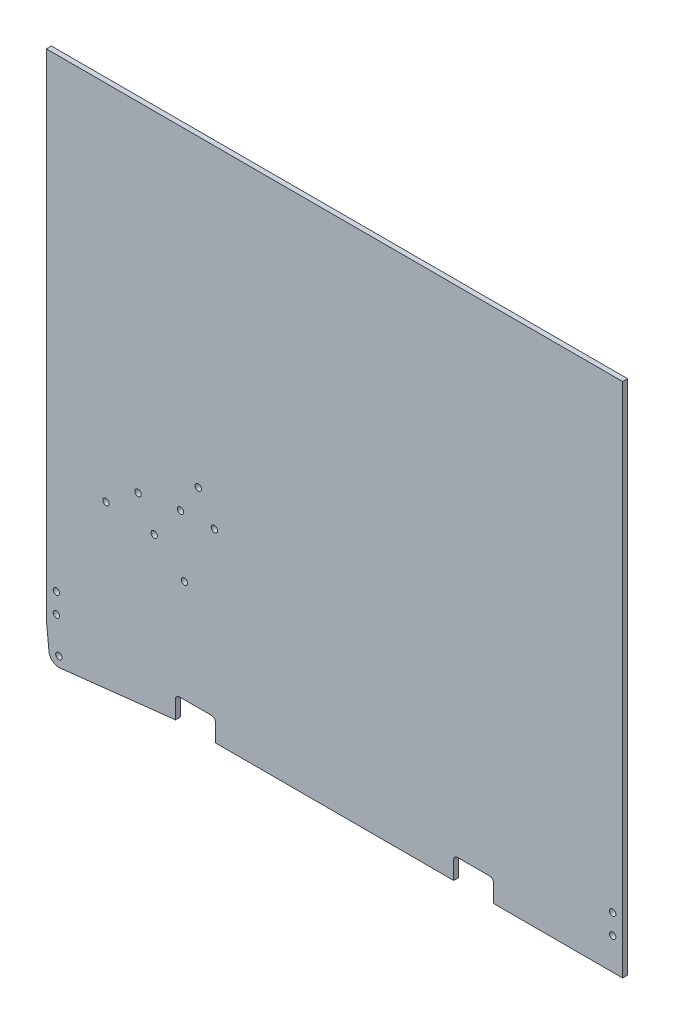
SolidWorks part; units mm, degrees
ref_plane "Front Plane" through (0, 0, 0) normal (0, 0, 1) x (1, 0, 0)
ref_plane "Top Plane" through (0, 0, 0) normal (0, 1, 0) x (1, 0, 0)
ref_plane "Right Plane" through (0, 0, 0) normal (1, 0, 0) x (0, 0, -1)
sketch "Sketch1" plane through (0, 0, 0) normal (0, 0, 1) x (1, 0, 0)
  line L0 (82.55, -20.32) -> (82.55, -6.35)
  line L2 (0, 0) -> (0, 309.88)
  line L3 (0, 309.88) -> (368.3, 309.88)
  line L4 (368.3, -20.32) -> (368.3, 309.88)
  line L5 (82.55, -6.35) -> (107.95, -6.35)
  line L6 (107.95, -6.35) -> (107.95, -20.32)
  line L7 (107.95, -20.32) -> (260.35, -20.32)
  line L8 (260.35, -20.32) -> (260.35, -6.35)
  line L9 (260.35, -6.35) -> (285.75, -6.35)
  line L10 (285.75, -6.35) -> (285.75, -20.32)
  line L11 (285.75, -20.32) -> (368.3, -20.32)
  line L12 (361.95, 12.7) -> (368.3, 12.7) construction
  line L13 (0, 0) -> (6.35, 0) construction
  line L14 (0.0315, -6.9818) -> (1.619, -22.8568)
  line L15 (8.6391, -28.5361) -> (82.55, -20.32)
  line L16 (0, 0) -> (0, -6.35)
  line L17 (85.725, 97.155) -> (82.9754, 95.5675) construction
  line L18 (97.0634, 115.6163) -> (58.5686, 93.3913) construction
  line L19 (97.0634, 115.6163) -> (107.3822, 97.7437) construction
  line L20 (58.5686, 93.3913) -> (68.8873, 75.5187) construction
  line L21 (107.3822, 97.7437) -> (68.8873, 75.5187) construction
  line L22 (97.0634, 115.6163) -> (68.8873, 75.5187) construction
  line L23 (58.5686, 93.3913) -> (107.3822, 97.7437) construction
  line L24 (7.9375, -22.225) -> (88.2169, 59.1366) construction
  circle A0 centre (6.35, 0) radius 2.032
  circle A1 centre (6.35, 12.7) radius 2.032
  circle A2 centre (361.95, 0) radius 2.032
  circle A3 centre (361.95, 12.7) radius 2.032
  arc A5 (1.619, -22.8568) -> (8.6391, -28.5361) centre (7.9375, -22.225) ccw
  circle A6 centre (7.9375, -22.225) radius 2.032
  arc A7 (0, -6.35) -> (0.0315, -6.9818) centre (6.35, -6.35) ccw
  circle A8 centre (38.1, 78.105) radius 2.032
  circle A9 centre (85.725, 97.155) radius 2.032
  circle A10 centre (58.5686, 93.3913) radius 2.032
  circle A11 centre (68.8873, 75.5187) radius 2.032
  circle A12 centre (107.3822, 97.7437) radius 2.032
  circle A13 centre (97.0634, 115.6163) radius 2.032
  circle A14 centre (88.2169, 59.1366) radius 2.032
  dimension "D6" = 4.064
  dimension "D10" = 6.35
  dimension "D11" = 4.064
  dimension "D17" = 38.1
  dimension "D2" = 330.2
  dimension "D3" = 13.97
  dimension "D4" = 25.4
  dimension "D5" = 152.4
  dimension "D7" = 12.7
  dimension "D8" = 6.35
  dimension "D9" = 20.32
  dimension "D12" = 22.225
  dimension "D13" = 1.5875
  dimension "D14" = 82.55
  dimension "D15" = 368.3
  dimension "D16" = 6.35
  dimension "D18" = 98.425
  dimension "D19" = 47.625
  dimension "D20" = 19.05
  dimension "D21" = 3.175
  dimension "D22" = 60
  dimension "D23" = 20.6375
  dimension "D24" = 44.45
  dimension "D25" = 38.1
  dimension "D26" = 114.3
extrude "Boss-Extrude1" add sketch "Sketch1" along normal blind 3.175
fillet "Fillet1" radius 2.286 4 edges at (285.75, -6.35, 1.5875) (107.95, -6.35, 1.5875) (260.35, -6.35, 1.5875) (82.55, -6.35, 1.5875)
